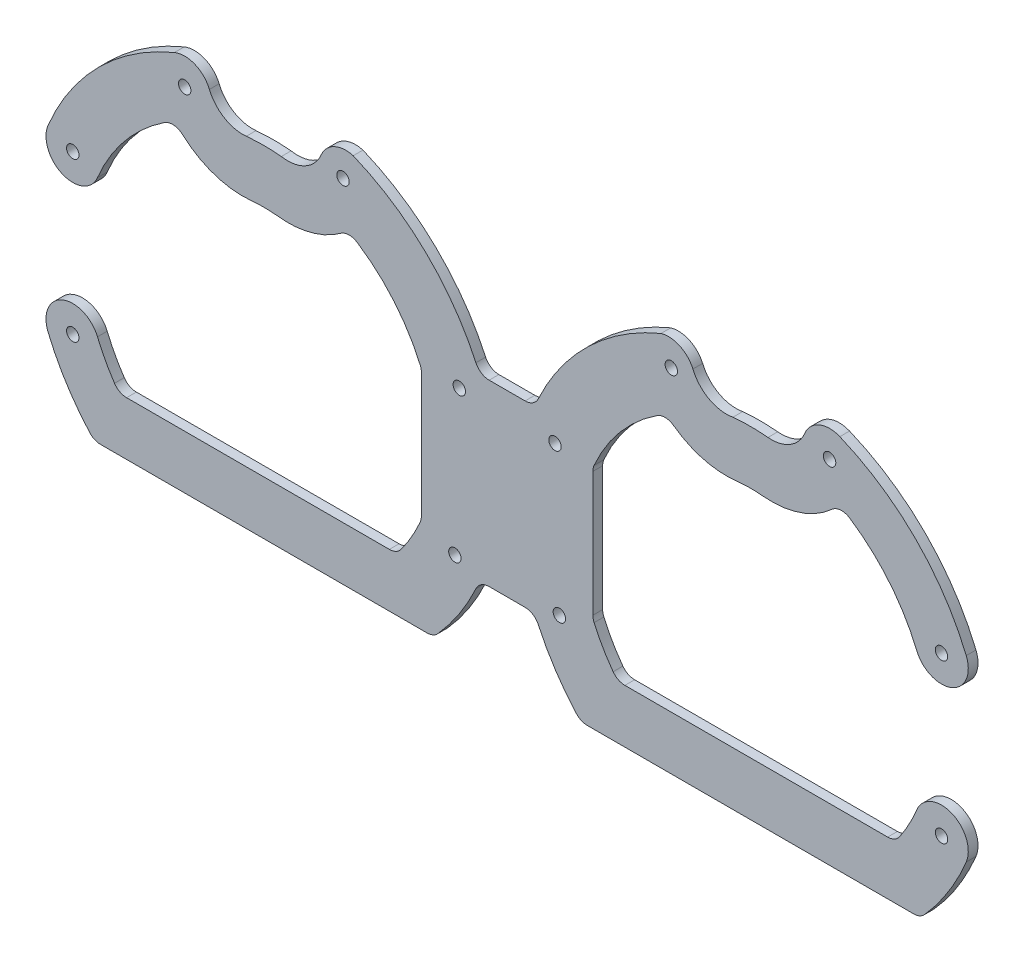
SolidWorks part; units mm, degrees
ref_plane "前视基准面" through (0, 0, 0) normal (0, 0, 1) x (1, 0, 0)
ref_plane "上视基准面" through (0, 0, 0) normal (0, 1, 0) x (1, 0, 0)
ref_plane "右视基准面" through (0, 0, 0) normal (1, 0, 0) x (0, 0, -1)
sketch "草图1" plane through (0, 0, 0) normal (0, 0, 1) x (1, 0, 0)
  line L3 (-50, 48) -> (50, 48)
  line L4 (-50, -48) -> (50, -48)
  arc A4 (-50, 48) -> (-50, -48) centre (-50, 0) ccw
  arc A5 (50, 48) -> (50, -48) centre (50, 0) cw
extrude "凸台-拉伸1" add sketch "草图1" along normal blind 2
hole_wizard "M2.5 螺旋的螺纹孔钻头1" positions "3D草图1" profile "草图3" hole size "M2.5x0.45" standard "BSI" end condition through all
sketch3d "3D草图1"
  point P56 (-89.2649, 16.264, 2)
  point P63 (-66.264, 39.2649, 2)
  point P77 (-33.736, 39.2649, 2)
  point P157 (-33.736, -39.2649, 2)
  point P158 (-66.264, -39.2649, 2)
  point P159 (-89.2649, -16.264, 2)
  point P196 (-9.8309, 13.8815, 2)
  point P198 (-10.7351, -16.264, 2)
  point P210 (10.7351, -16.264, 2)
  point P211 (9.8309, 13.8815, 2)
  point P212 (89.2649, -16.264, 2)
  point P213 (66.264, -39.2649, 2)
  point P214 (33.736, -39.2649, 2)
  point P215 (33.736, 39.2649, 2)
  point P216 (66.264, 39.2649, 2)
  point P217 (89.2649, 16.264, 2)
sketch "草图3" plane through (-89.2649, 16.264, 2) normal (1, 0, 0) x (0, -1, 0)
  line L0 (0, 0) -> (0, 2)
  line L1 (0, 2) -> (1.275, 2)
  line L2 (1.275, 2) -> (1.275, 0)
  line L5 (1.275, 0) -> (0, 0)
  line L11 (0, -6.35) -> (0, 107.95) construction
  dimension "通孔孔直径" = 2.55
  dimension "通孔孔深度" = 2
sketch "草图5" plane through (0, 0, 0) normal (0, 0, 1) x (1, 0, 0)
  line L0 (-17.6246, 13.4103) -> (-17.6246, -13.4103)
  line L2 (1.1, 0) -> (-1.1, 0) construction
  line L6 (-5.6538, -18.3688) -> (5.6538, -18.3688)
  line L7 (-50, -22) -> (-22.7236, -22)
  line L8 (-50, -22) -> (-79.7489, -22)
  line L9 (-5.6538, 18.3688) -> (5.6538, 18.3688)
  line L10 (-50, -33) -> (-84.8569, -33)
  line L11 (-50, -33) -> (-15.1431, -33)
  line L12 (0, -1.1) -> (0, 1.1) construction
  line L13 (50, -33) -> (15.1431, -33)
  line L14 (50, -33) -> (84.8569, -33)
  line L16 (50, -22) -> (79.7489, -22)
  line L17 (50, -22) -> (22.7236, -22)
  line L19 (17.6246, 13.4103) -> (17.6246, -13.4103)
  arc A5 (-68.3688, 44.3462) -> (-61.1827, 41.3696) centre (-66.264, 39.2649) cw
  arc A9 (-50, 48) -> (-50, -48) centre (-50, 0) ccw construction
  arc A10 (-61.1827, 41.3696) -> (-53.601, 36.8218) centre (-54.3236, 44.2108) ccw
  arc A11 (-53.601, 36.8218) -> (-46.399, 36.8218) centre (-50, 0) cw
  arc A12 (-52.5304, 25.874) -> (-68.272, 32.1735) centre (-54.3236, 44.2108) cw
  arc A14 (-68.3688, 44.3462) -> (-94.3462, 18.3688) centre (-50, 0) ccw
  arc A15 (-52.5304, 25.874) -> (-47.4696, 25.874) centre (-50, 0) cw
  arc A16 (-84.1835, 14.1593) -> (-68.272, 32.1735) centre (-50, 0) cw
  arc A17 (-84.1835, 14.1593) -> (-94.3462, 18.3688) centre (-89.2649, 16.264) cw
  arc A19 (-17.6246, 13.4103) -> (-32.6946, 30.4716) centre (-50, 0) ccw
  arc A20 (-31.6312, 44.3462) -> (-5.6538, 18.3688) centre (-50, 0) cw
  arc A21 (-47.4696, 25.874) -> (-32.6946, 30.4716) centre (-45.0502, 44.1387) ccw
  arc A22 (-38.1764, 41.2915) -> (-46.399, 36.8218) centre (-45.0502, 44.1387) cw
  arc A23 (-31.6312, 44.3462) -> (-38.1764, 41.2915) centre (-33.1495, 39.0599) ccw
  arc A29 (-84.1835, -14.1593) -> (-94.3462, -18.3688) centre (-89.2649, -16.264) ccw
  arc A63 (-79.7489, -22) -> (-84.1835, -14.1593) centre (-50, 0) cw
  arc A64 (-22.7236, -22) -> (-17.6246, -13.4103) centre (-50, 0) ccw
  arc A65 (-15.1431, -33) -> (-5.6538, -18.3688) centre (-50, 0) ccw
  arc A66 (-84.8569, -33) -> (-94.3462, -18.3688) centre (-50, 0) cw
  arc A67 (84.8569, -33) -> (94.3462, -18.3688) centre (50, 0) ccw
  arc A68 (15.1431, -33) -> (5.6538, -18.3688) centre (50, 0) cw
  arc A69 (22.7236, -22) -> (17.6246, -13.4103) centre (50, 0) cw
  arc A70 (79.7489, -22) -> (84.1835, -14.1593) centre (50, 0) ccw
  arc A71 (84.1835, -14.1593) -> (94.3462, -18.3688) centre (89.2649, -16.264) cw
  arc A72 (31.6312, 44.3462) -> (38.1764, 41.2915) centre (33.1495, 39.0599) cw
  arc A73 (38.1764, 41.2915) -> (46.399, 36.8218) centre (45.0502, 44.1387) ccw
  arc A74 (47.4696, 25.874) -> (32.6946, 30.4716) centre (45.0502, 44.1387) cw
  arc A75 (31.6312, 44.3462) -> (5.6538, 18.3688) centre (50, 0) ccw
  arc A76 (17.6246, 13.4103) -> (32.6946, 30.4716) centre (50, 0) cw
  arc A77 (84.1835, 14.1593) -> (94.3462, 18.3688) centre (89.2649, 16.264) ccw
  arc A78 (84.1835, 14.1593) -> (68.272, 32.1735) centre (50, 0) ccw
  arc A79 (52.5304, 25.874) -> (47.4696, 25.874) centre (50, 0) ccw
  arc A80 (68.3688, 44.3462) -> (94.3462, 18.3688) centre (50, 0) cw
  arc A81 (52.5304, 25.874) -> (68.272, 32.1735) centre (54.3236, 44.2108) ccw
  arc A82 (53.601, 36.8218) -> (46.399, 36.8218) centre (50, 0) ccw
  arc A83 (61.1827, 41.3696) -> (53.601, 36.8218) centre (54.3236, 44.2108) cw
  arc A84 (68.3688, 44.3462) -> (61.1827, 41.3696) centre (66.264, 39.2649) ccw
  point P54 (-17.6246, 0)
  point P74 (17.6246, 0)
extrude "切除-拉伸1" cut sketch "草图5" along normal blind 10 flip side to cut
fillet "圆角1" radius 3 20 edges at (68.272, 32.1735, 1) (32.6946, 30.4716, 1) (17.6246, 13.4103, 1) (17.6246, -13.4103, 1) (22.7236, -22, 1) (79.7489, -22, 1) (84.8569, -33, 1) (15.1431, -33, 1) (-5.6538, -18.3688, 1) (5.6538, -18.3688, 1) (5.6538, 18.3688, 1) (-5.6538, 18.3688, 1) (-15.1431, -33, 1) (-79.7489, -22, 1) (-22.7236, -22, 1) (-17.6246, -13.4103, 1) (-17.6246, 13.4103, 1) (-32.6946, 30.4716, 1) (-68.272, 32.1735, 1) (-84.8569, -33, 1)
